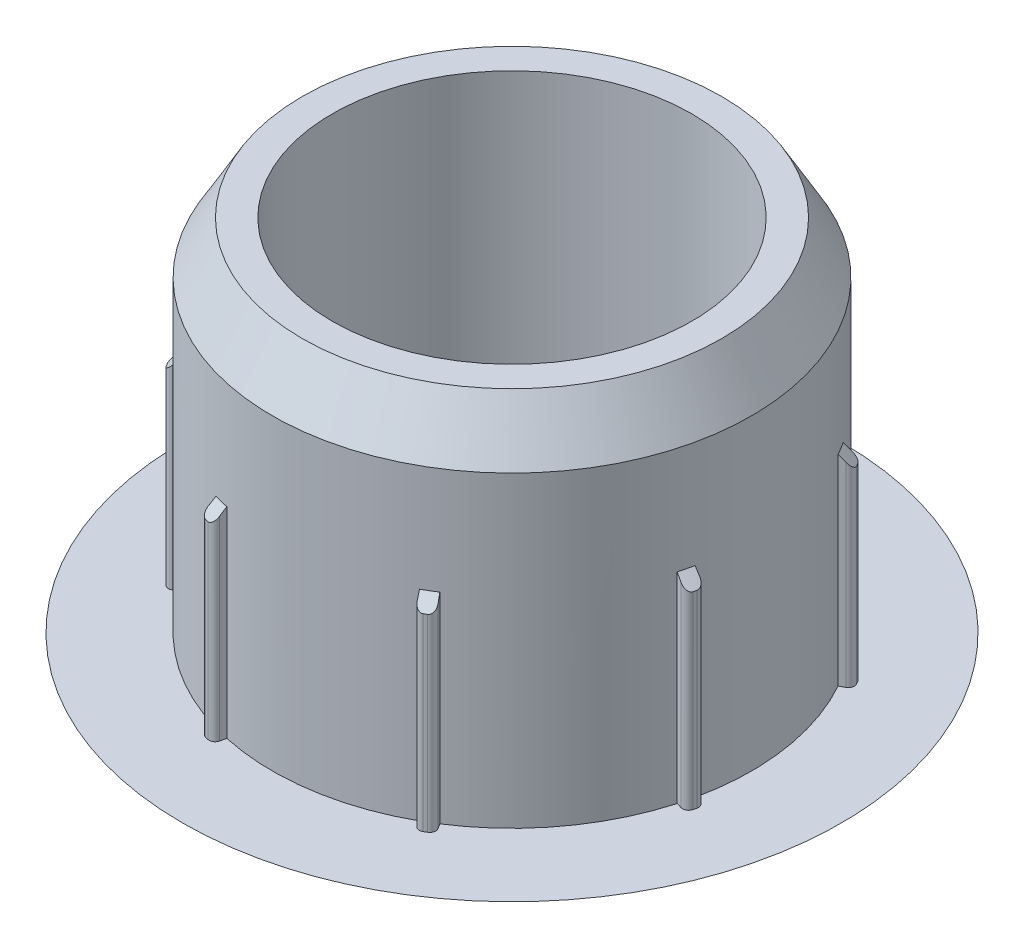
SolidWorks part; units mm, degrees
ref_plane "Plan de face" through (0, 0, 0) normal (0, 0, 1) x (1, 0, 0)
ref_plane "Plan de dessus" through (0, 0, 0) normal (0, 1, 0) x (1, 0, 0)
ref_plane "Plan de droite" through (0, 0, 0) normal (1, 0, 0) x (0, 0, -1)
sketch "Esquisse1" plane through (0, 0, 0) normal (0, 0, 1) x (1, 0, 0)
  line L0 (-5.8446, 3.7949) -> (-5.8446, -2.2051)
  line L1 (-5.8446, -2.2051) -> (-7.3446, -2.2051)
  line L2 (-7.3446, -2.2051) -> (-7.3446, -3.2051)
  line L3 (-7.3446, -3.2051) -> (-1.8446, -3.2051)
  line L4 (-1.8446, -3.2051) -> (-1.8446, -2.2051)
  line L5 (-1.8446, -2.2051) -> (-4.8446, -2.2051)
  line L6 (-4.8446, -2.2051) -> (-4.8446, 3.7949)
  line L7 (-4.8446, 3.7949) -> (-5.8446, 3.7949)
  dimension "D1" = 4
  dimension "D2" = 1.5
  dimension "D3" = 6
  dimension "D4" = 1
  dimension "D5" = 1
revolve "Révolution1" add sketch "Esquisse1" angle 360 about L4
chamfer "Chanfrein2" distance 1 angle 60 1 edges at (-1.8446, -3.2051, -5.5) first distance on face at (-1.8446, -3.2051, -5.5)
chamfer "Chanfrein3" distance 0.5 angle 60 1 edges at (-1.8446, 3.7949, -4) first distance on face at (-1.8446, 3.7949, -4)
sketch "Esquisse2" plane through (0, 0, 0) normal (0, 0, 1) x (1, 0, 0)
  line L0 (-5.8446, 1.1443) -> (-6.0919, 1.1443)
  line L1 (-5.8446, 2.9288) -> (-5.8446, -2.2051) construction
  line L2 (-6.0919, 1.1443) -> (-6.0919, -2.2051)
  line L3 (3.6554, -2.2051) -> (-7.3446, -2.2051) construction
  line L4 (-6.0919, -2.2051) -> (-5.8446, -2.2051)
  line L5 (-5.8446, -2.2051) -> (-5.8446, 1.1443)
wrap "Enroulement2" sketch "Esquisse2" wrap type emboss source sketch "Esquisse2" thickness 0.2 face at (-1.8446, 2.9288, -4) parameters "D1"=0.2
pattern_circular "Répétition circulaire3" count 8 every 45 about axis through (-1.8446, 2.9288, 0) along (0, -1, 0) of "Enroulement2"
chamfer "Chanfrein4" distance 0.2 angle 45 8 edges at (-2.8654, 1.1443, 4.074) (0.3144, 1.1443, 3.6026) (2.2295, 1.1443, 1.0209) (1.7581, 1.1443, -2.1589) (-0.8237, 1.1443, -4.074) (-4.0035, 1.1443, -3.6026) (-5.9186, 1.1443, -1.0209) (-5.4472, 1.1443, 2.1589)
fillet "Congé1" radius 0.1 16 edges at (-5.9482, -0.6304, -0.8944) (-5.8851, -0.6304, -1.1463) (-4.1138, -0.6304, -3.5342) (-3.8911, -0.6304, -3.6677) (-0.6982, -0.6304, -4.0405) (-0.9501, -0.6304, -4.1037) (1.8231, -0.6304, -2.0465) (1.6896, -0.6304, -2.2693) (2.196, -0.6304, 1.1463) (2.2591, -0.6304, 0.8944) (0.2019, -0.6304, 3.6677) (0.4247, -0.6304, 3.5342) (-2.739, -0.6304, 4.1037) (-2.9909, -0.6304, 4.0405) (-5.5122, -0.6304, 2.0465) (-5.3787, -0.6304, 2.2693)
